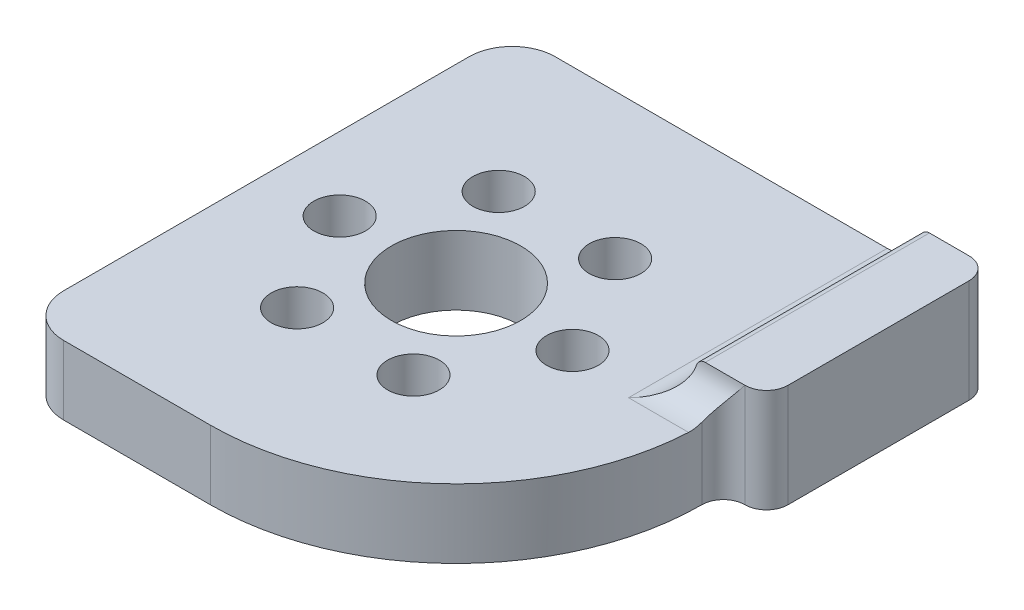
SolidWorks part; units mm, degrees
ref_plane "前视基准面" through (0, 0, 0) normal (0, 0, 1) x (1, 0, 0)
ref_plane "上视基准面" through (0, 0, 0) normal (0, 1, 0) x (1, 0, 0)
ref_plane "右视基准面" through (0, 0, 0) normal (1, 0, 0) x (0, 0, -1)
sketch "草图1" plane through (0, 0, 0) normal (0, 1, 0) x (1, 0, 0)
  line L0 (0, 28.5) -> (-22, 28.5)
  line L1 (-22, 28.5) -> (-22, -28.5)
  line L2 (0, -28.5) -> (-22, -28.5)
  line L3 (0, 28.5) -> (0, -28.5) construction
  line L4 (0, 28.5) -> (33.5, 28.5)
  line L5 (33.5, 28.5) -> (33.5, 2.5)
  line L8 (28.5, 0) -> (28.5, 2.5)
  line L9 (28.5, 2.5) -> (33.5, 2.5)
  arc A0 (0, -28.5) -> (28.5, 0) centre (0, 0) ccw
  dimension "D1" = 33.5
  dimension "D2" = 22
  dimension "D3" = 57
  dimension "D4" = 28.5
  dimension "D5" = 2.5
extrude "凸台-拉伸1" add sketch "草图1" along normal blind 8
sketch "草图2" plane through (0, 8, 0) normal (0, 1, 0) x (1, 0, 0)
  circle A0 centre (0, 0) radius 13.5 construction
  circle A1 centre (-13.5, 0) radius 1.75
  circle A2 centre (-6.75, 11.6913) radius 1.75
  circle A3 centre (6.75, 11.6913) radius 1.75
  circle A4 centre (13.5, 0) radius 1.75
  circle A5 centre (6.75, -11.6913) radius 1.75
  circle A6 centre (-6.75, -11.6913) radius 1.75
  point P18 (0, 0)
  dimension "D1" = 27
  dimension "D2" = 3.5
  dimension "D3" = 6
extrude "切除-拉伸1" cut sketch "草图2" against normal blind 16
sketch "草图4" plane through (0, 8, 0) normal (0, 1, 0) x (1, 0, 0)
  line L0 (33.5, 28.5) -> (-22, 28.5) construction
  line L1 (33.5, 2.5) -> (25.5, 2.5)
  line L2 (33.5, 2.5) -> (33.5, 28.5)
  line L3 (33.5, 28.5) -> (25.5, 28.5)
  line L4 (25.5, 2.5) -> (25.5, 28.5)
  dimension "D1" = 8
extrude "凸台-拉伸3" add sketch "草图4" along normal blind 4
fillet "圆角2" radius 2.5 2 edges at (33.5, 6, -2.5) (28.5, 4, -2.5)
fillet "圆角3" radius 4 1 edges at (25.5, 8, -15.5)
fillet "圆角4" radius 4 1 edges at (26.25, 8, -2.5)
fillet "圆角5" radius 2.5 1 edges at (33.5, 6, -28.5)
fillet "圆角6" radius 5 2 edges at (-22, 4, 28.5) (-22, 4, -28.5)
sketch "草图5" plane through (0, 8, 0) normal (0, 1, 0) x (1, 0, 0)
  circle A0 centre (0, 0) radius 13.5 construction
  circle A1 centre (-13.5, 0) radius 3
  circle A2 centre (-6.75, 11.6913) radius 3
  circle A3 centre (6.75, 11.6913) radius 3
  circle A4 centre (13.5, 0) radius 3
  circle A5 centre (6.75, -11.6913) radius 3
  circle A6 centre (-6.75, -11.6913) radius 3
  point P18 (0, 0)
  dimension "D1" = 6
  dimension "D2" = 6
extrude "切除-拉伸2" cut sketch "草图5" against normal blind 5
fillet "圆角7" radius 1 1 edges at (25.5, 12, -15.5)
sketch "草图6" plane through (0, 8, 0) normal (0, 1, 0) x (1, 0, 0)
  circle A0 centre (0, 0) radius 7.5
  dimension "D1" = 15
extrude "切除-拉伸3" cut sketch "草图6" against normal blind 10
